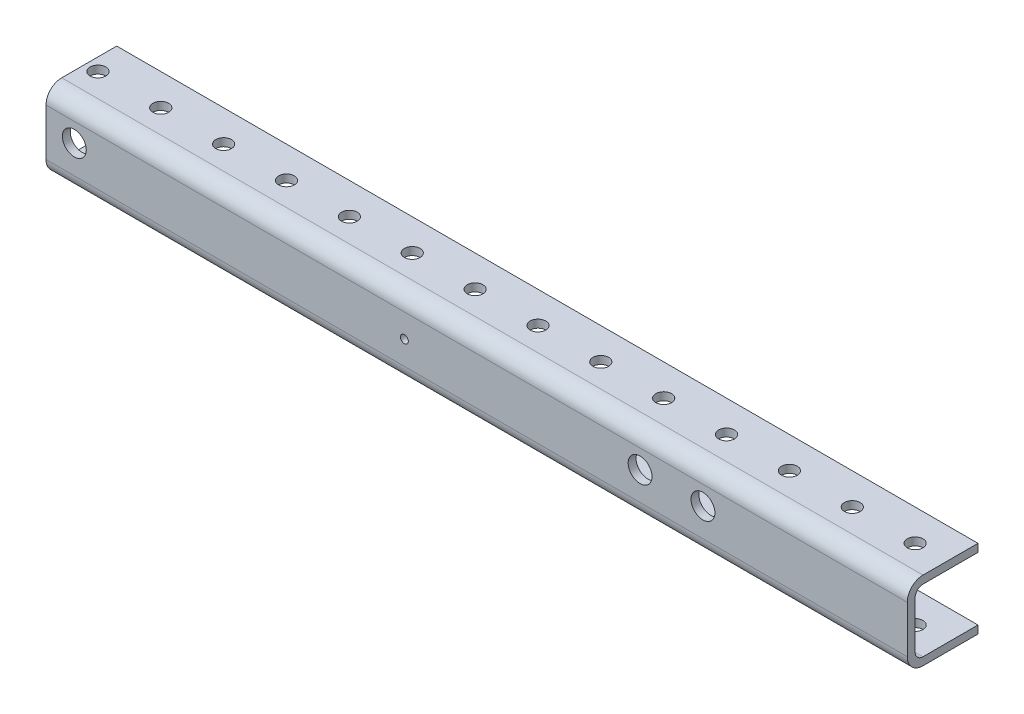
SolidWorks part; units mm, degrees
material "5052-O, Rod (SS)"
ref_plane "Front Plane" through (0, 0, 0) normal (0, 0, 1) x (1, 0, 0)
ref_plane "Top Plane" through (0, 0, 0) normal (0, 1, 0) x (1, 0, 0)
ref_plane "Right Plane" through (0, 0, 0) normal (1, 0, 0) x (0, 0, -1)
ref_plane "Plane1" through (0, 0, 3.175) normal (0, 0, 1) x (1, 0, 0)
sketch "Sketch1" plane through (0, 0, 3.175) normal (0, 0, 1) x (1, 0, 0)
  line L0 (872.98, -7.202) -> (872.98, 24.548)
  line L1 (872.98, 24.548) -> (-16.02, 24.548)
  line L2 (-16.02, 24.548) -> (-16.02, -7.202)
  line L3 (-16.02, -7.202) -> (872.98, -7.202)
extrude "Extrude1" add sketch "Sketch1" against normal blind 28.575
sketch "Sketch2" plane through (-16.02, 0, 0) normal (-1, 0, 0) x (0, 0, 1)
  line L0 (-25.4, 21.373) -> (-25.4, -4.027)
  line L1 (-25.4, -4.027) -> (0, -4.027)
  line L2 (0, -4.027) -> (0, 21.373)
  line L3 (0, 21.373) -> (-25.4, 21.373)
extrude "Extrude2" cut sketch "Sketch2" against normal up to next
hole_wizard "Hole1" positions "Sketch4" profile "Sketch3" legacy
sketch "Sketch4" plane through (0, 24.548, 0) normal (0, 1, 0) x (-1, 0, 0)
  point P0 (3.32, -12.7)
sketch "Sketch3" plane through (-3.32, 24.548, -12.7) normal (1, 0, 0) x (0, 0, 1)
  line L0 (0, 0) -> (0, 3.175)
  line L1 (0, 3.175) -> (3.175, 3.175)
  line L2 (3.175, 3.175) -> (3.175, 0)
  line L3 (3.175, 0) -> (0, 0)
  line L4 (0, 110) -> (0, -10) construction
  dimension "Diameter" = 6.35
  dimension "Depth" = 3.175
sketch3d "3DSketch1"
  point P0 (428.6664, 8.6668, -7.2024)
  point P1 (528.6664, 8.6668, -7.2024)
ref_axis "Axis1" through (528.6664, 8.6668, -7.2024) along (-1, 0, 0)
pattern_linear "LPattern1" count 35 spacing 25.4 along (1, 0, 0) of "Hole1"
hole_wizard "Hole2" positions "Sketch6" profile "Sketch5" legacy
sketch "Sketch6" plane through (0, 0, 3.175) normal (0, 0, 1) x (1, 0, 0)
  point P0 (66.53, 10.578)
sketch "Sketch5" plane through (66.53, 10.578, 3.175) normal (1, 0, 0) x (0, -1, 0)
  line L0 (0, 0) -> (0, 3.175)
  line L1 (0, 3.175) -> (4.826, 3.175)
  line L2 (4.826, 3.175) -> (4.826, 0)
  line L3 (4.826, 0) -> (0, 0)
  line L4 (0, 110) -> (0, -10) construction
  dimension "Diameter" = 9.652
  dimension "Depth" = 3.175
sketch3d "3DSketch2"
  point P0 (428.8468, 8.4517, -7.1294)
  point P1 (528.8468, 8.4517, -7.1294)
ref_axis "Axis2" through (528.8468, 8.4517, -7.1294) along (-1, 0, 0)
pattern_linear "LPattern2" count 12 spacing 25.4 along (1, 0, 0) skipping (2, 0), (3, 0), (4, 0), (5, 0), (6, 0), (7, 0), (8, 0), (9, 0) of "Hole2"
hole_wizard "Hole3" positions "Sketch8" profile "Sketch7" legacy
sketch "Sketch8" plane through (0, 0, 3.175) normal (0, 0, 1) x (1, 0, 0)
  point P0 (428.48, 6.768)
sketch "Sketch7" plane through (428.48, 6.768, 3.175) normal (1, 0, 0) x (0, -1, 0)
  line L0 (0, 0) -> (0, 3.175)
  line L1 (0, 3.175) -> (4.826, 3.175)
  line L2 (4.826, 3.175) -> (4.826, 0)
  line L3 (4.826, 0) -> (0, 0)
  line L4 (0, 110) -> (0, -10) construction
  dimension "Diameter" = 9.652
  dimension "Depth" = 3.175
hole_wizard "Hole4" positions "Sketch10" profile "Sketch9" legacy
sketch "Sketch10" plane through (0, 0, 3.175) normal (0, 0, 1) x (1, 0, 0)
  point P0 (511.03, 10.578)
sketch "Sketch9" plane through (511.03, 10.578, 3.175) normal (1, 0, 0) x (0, -1, 0)
  line L0 (0, 0) -> (0, 3.175)
  line L1 (0, 3.175) -> (4.826, 3.175)
  line L2 (4.826, 3.175) -> (4.826, 0)
  line L3 (4.826, 0) -> (0, 0)
  line L4 (0, 110) -> (0, -10) construction
  dimension "Diameter" = 9.652
  dimension "Depth" = 3.175
sketch3d "3DSketch3"
  point P0 (429.3014, 8.4448, -7.1738)
  point P1 (529.3014, 8.4448, -7.1738)
ref_axis "Axis3" through (529.3014, 8.4448, -7.1738) along (-1, 0, 0)
pattern_linear "LPattern3" count 12 spacing 25.4 along (1, 0, 0) skipping (2, 0), (3, 0), (4, 0), (5, 0), (6, 0), (7, 0), (8, 0), (9, 0) of "Hole4"
hole_wizard "Hole5" positions "Sketch12" profile "Sketch11" legacy
sketch "Sketch12" plane through (0, 0, 3.175) normal (0, 0, 1) x (1, 0, 0)
  point P0 (669.78, 8.673)
sketch "Sketch11" plane through (669.78, 8.673, 3.175) normal (1, 0, 0) x (0, -1, 0)
  line L0 (0, 0) -> (0, 3.175)
  line L1 (0, 3.175) -> (1.5875, 3.175)
  line L2 (1.5875, 3.175) -> (1.5875, 0)
  line L3 (1.5875, 0) -> (0, 0)
  line L4 (0, 110) -> (0, -10) construction
  dimension "Diameter" = 3.175
  dimension "Depth" = 3.175
hole_wizard "Hole6" positions "Sketch14" profile "Sketch13" legacy
sketch "Sketch14" plane through (0, -4.027, 0) normal (0, 1, 0) x (-1, 0, 0)
  point P0 (3.32, -12.7)
sketch "Sketch13" plane through (-3.32, -4.027, -12.7) normal (1, 0, 0) x (0, 0, 1)
  line L0 (0, 0) -> (0, 3.175)
  line L1 (0, 3.175) -> (3.175, 3.175)
  line L2 (3.175, 3.175) -> (3.175, 0)
  line L3 (3.175, 0) -> (0, 0)
  line L4 (0, 110) -> (0, -10) construction
  dimension "Diameter" = 6.35
  dimension "Depth" = 3.175
sketch3d "3DSketch4"
  point P0 (428.6444, 8.4444, -7.1991)
  point P1 (528.6444, 8.4444, -7.1991)
ref_axis "Axis4" through (528.6444, 8.4444, -7.1991) along (-1, 0, 0)
pattern_linear "LPattern4" count 35 spacing 25.4 along (1, 0, 0) of "Hole6"
fillet "Fillet1" radius 3.175 1 edges at (428.48, 21.373, 0) tangent propagation no
fillet "Fillet2" radius 3.175 1 edges at (428.48, -4.027, 0) tangent propagation no
fillet "Fillet3" radius 6.35 1 edges at (428.48, -7.202, 3.175) tangent propagation no
fillet "Fillet4" radius 6.35 1 edges at (428.48, 24.548, 3.175) tangent propagation no
ref_plane "Plane2" through (872.98, 24.548, -3.175) normal (1, 0, 0) x (0, 0, -1)
sketch "Sketch16" plane through (0, 24.548, 0) normal (0, 1, 0) x (1, 0, 0)
  line L0 (112.98, 3.175) -> (112.98, 25.4) construction
  line L1 (-16.02, 3.175) -> (872.98, 3.175) construction
  line L2 (872.98, 25.4) -> (-16.02, 25.4) construction
  line L3 (872.98, 25.4) -> (872.98, 3.175) construction
  line L6 (112.98, 3.175) -> (112.98, 25.4)
  line L7 (112.98, 25.4) -> (-16.02, 25.4)
  line L9 (112.98, 25.4) -> (-32.7801, 25.4)
  line L10 (112.98, 25.4) -> (112.98, -46.1048)
  line L11 (112.98, -46.1048) -> (-32.7801, -46.1048)
  line L12 (-32.7801, 25.4) -> (-32.7801, -46.1048)
  dimension "D1" = 760
extrude "Cut-Extrude2" cut sketch "Sketch16" against normal blind 75 contours L10 L11 L12 L9
sketch "Sketch17" plane through (0, 24.548, 0) normal (0, 1, 0) x (1, 0, 0)
  line L0 (524.98, 3.175) -> (524.98, 25.4) construction
  line L1 (112.98, 3.175) -> (872.98, 3.175) construction
  line L2 (872.98, 25.4) -> (112.98, 25.4) construction
  line L3 (872.98, 25.4) -> (872.98, 3.175) construction
  line L5 (524.98, 25.4) -> (51.3514, 25.4)
  line L6 (524.98, 25.4) -> (524.98, -41.5089)
  line L7 (524.98, -41.5089) -> (51.3514, -41.5089)
  line L8 (51.3514, 25.4) -> (51.3514, -41.5089)
  dimension "D1" = 348
extrude "Cut-Extrude3" cut sketch "Sketch17" against normal blind 186
